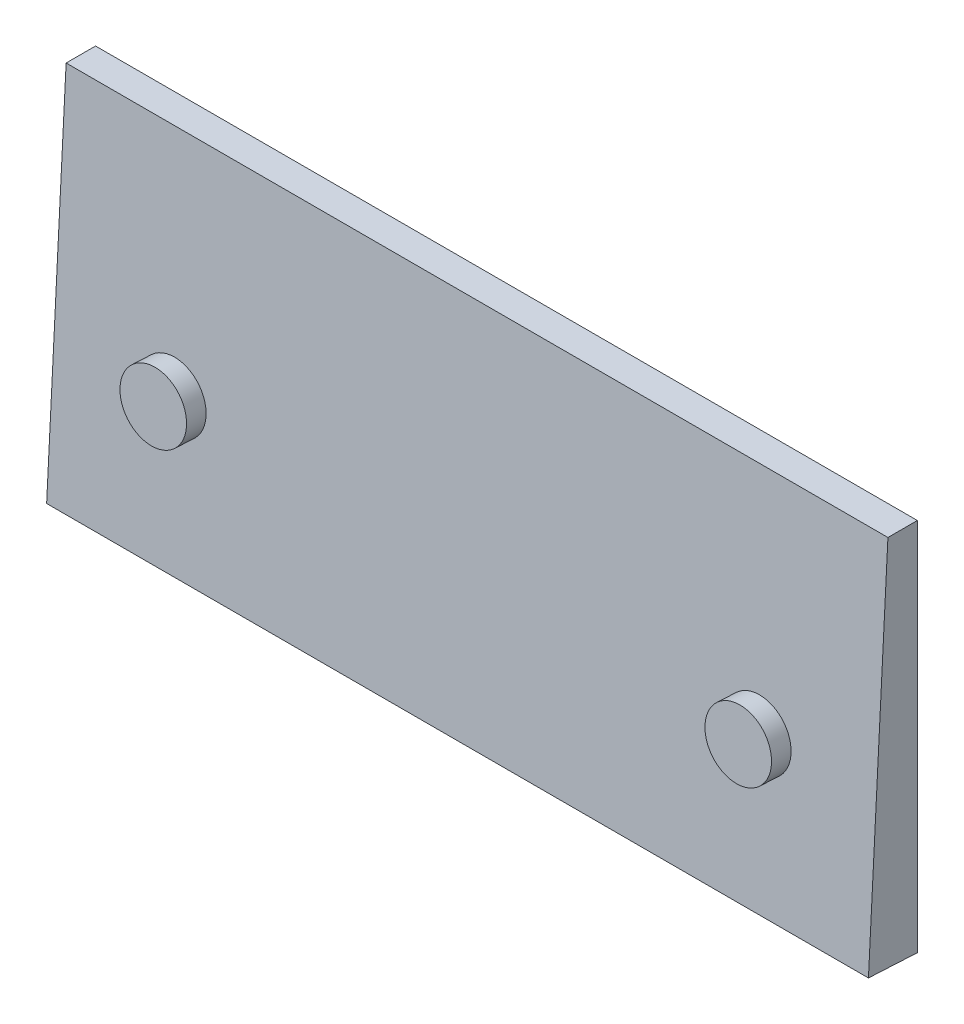
SolidWorks part; units mm, degrees
ref_plane "Top Plane" through (0, 0, 0) normal (0, 0, 1) x (1, 0, 0)
ref_plane "Front Plane" through (0, 0, 0) normal (0, 1, 0) x (1, 0, 0)
ref_plane "Right Plane" through (0, 0, 0) normal (1, 0, 0) x (0, 0, -1)
sketch "Sketch1" plane through (0, 0, 0) normal (0, 0, 1) x (1, 0, 0)
  line L1 (-42, -19) -> (42, -19)
  line L2 (-42, -19) -> (-42, 19)
  line L3 (-42, 19) -> (42, 19)
  line L4 (42, -19) -> (42, 19)
  line L5 (-42, -19) -> (42, 19) construction
  line L6 (-42, 19) -> (42, -19) construction
  point P0 (0, 0)
  dimension "D1" = 38
  dimension "D2" = 84
extrude "Boss-Extrude1" add sketch "Sketch1" along normal blind 5
sketch "Sketch2" plane through (0, 0, 5) normal (0, 0, 1) x (1, 0, 0)
  line L1 (-42, -19) -> (42, -19)
  line L2 (-42, -19) -> (-42, 23)
  line L3 (-42, 23) -> (42, 23)
  line L4 (42, -19) -> (42, 23)
  dimension "D1" = 84
  dimension "D2" = 42
revolve "Cut-Revolve1" cut sketch "Sketch2" angle 3 about L1 reverse direction yes
sketch "Sketch4" plane through (0, 0.2093, 3.9933) normal (0, 0.0523, 0.9986) x (1, 0, 0)
  circle A3 centre (29.8957, -4.0835) radius 3.4
  circle A4 centre (-29.8957, -4.0835) radius 3.4
  dimension "D1" = 6.8
  dimension "D2" = 6.8
extrude "Boss-Extrude2" add sketch "Sketch4" along normal blind 2
sketch "Sketch5" plane through (0, -19, 0) normal (0, -1, 0) x (1, 0, 0)
  line L1 (-42, 0) -> (42, 0)
  line L2 (-42, 0) -> (-42, 5)
  line L3 (-42, 5) -> (42, 5)
  line L4 (42, 0) -> (42, 5)
revolve "Revolve1" add sketch "Sketch5" angle 3 about L3 reverse direction yes
